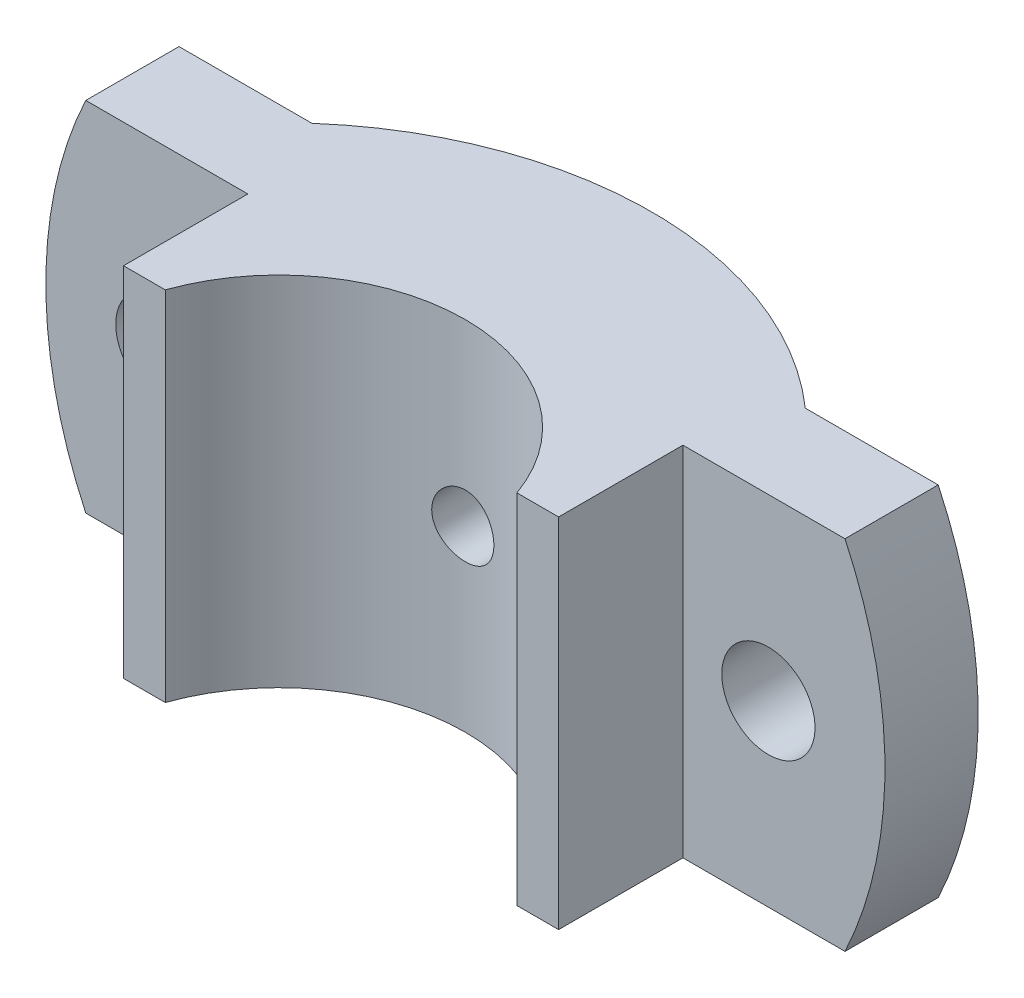
SolidWorks part; units mm, degrees
ref_plane "Front Plane" through (0, 0, 0) normal (0, 0, 1) x (1, 0, 0)
ref_plane "Top Plane" through (0, 0, 0) normal (0, 1, 0) x (1, 0, 0)
ref_plane "Right Plane" through (0, 0, 0) normal (1, 0, 0) x (0, 0, -1)
sketch "Sketch1" plane through (0, 0, 0) normal (0, 1, 0) x (1, 0, 0)
  line L0 (-67.1596, 0) -> (80.945, 0) construction
  line L1 (0, 82.0377) -> (0, -82.0377) construction
  line L2 (-54, 0) -> (-28, 0)
  line L3 (-54, 12) -> (-31.749, 12)
  line L4 (-28, -16) -> (-22.6274, -16)
  line L5 (22.6274, -16) -> (28, -16)
  line L6 (31.749, 12) -> (54, 12)
  line L7 (-54, 12) -> (-54, 0)
  line L8 (54, 12) -> (54, 0)
  line L9 (-28, 0) -> (-28, -16)
  line L10 (28, 0) -> (28, -16)
  line L11 (28, 0) -> (54, 0)
  arc A1 (22.6274, -16) -> (-22.6274, -16) centre (0, -24) ccw
  arc A2 (31.749, 12) -> (-31.749, 12) centre (0, -24) ccw
  point P7 (0, 24)
  dimension "D5" = 48
  dimension "D6" = 24
  dimension "D1" = 108
  dimension "D2" = 12
  dimension "D3" = 16
  dimension "D4" = 28
  dimension "D7" = 8
  dimension "D8" = 54
extrude "Boss-Extrude1" add sketch "Sketch1" along normal blind 46
sketch "Sketch2" plane through (0, 0, -12) normal (0, 0, -1) x (-1, 0, 0)
  line L0 (0, 57.651) -> (0, -11.651) construction
  line L1 (-77.2878, 23) -> (77.2878, 23) construction
  line L2 (-54, 46) -> (-48.8569, 46)
  line L3 (-54, 0) -> (-48.8569, 0)
  line L4 (-54, 46) -> (-54, 0)
  line L5 (54, 46) -> (54, 0)
  line L6 (39, 0) -> (39, 6)
  line L7 (48.8569, 46) -> (54, 46)
  line L8 (48.8569, 0) -> (54, 0)
  line L9 (-39, 46) -> (-39, 40)
  line L10 (-54, 46) -> (-31.749, 46) construction
  line L11 (-39, 0) -> (-39, 6)
  line L12 (39, 46) -> (39, 40)
  line L13 (-48.8569, 46) -> (-39, 46)
  line L14 (-48.8569, 0) -> (-39, 0)
  line L15 (48.8569, 46) -> (39, 46)
  line L16 (48.8569, 0) -> (39, 0)
  circle A0 centre (-39, 23) radius 6
  circle A1 centre (39, 23) radius 6
  arc A2 (-48.8569, 46) -> (-48.8569, 0) centre (0, 23) ccw
  arc A3 (48.8569, 0) -> (48.8569, 46) centre (0, 23) ccw
  arc A5 (-39, 6) -> (-39, 40) centre (-39, 23) ccw
  arc A6 (39, 6) -> (39, 40) centre (39, 23) cw
  point P11 (0, 23)
  line M4 (31.749, 0) -> (54, 0)
  line M5 (54, 0) -> (54, 46)
  line M6 (54, 46) -> (31.749, 46)
  line M7 (31.749, 46) -> (31.749, 0)
  dimension "D3" = 12
  dimension "D4" = 108
  dimension "D5" = 17
  dimension "D1" = 39
  dimension "D2" = 23
extrude "Cut-Extrude1" cut sketch "Sketch2" against normal through all contours A2 L2 L4 | A2 L4 L3 | A0 | A1 | A3 L5 M6 | A3 M4 M5 region at (52.4705, 40.3062, -12) region at (52.4705, 5.6938, -12) region at (-52.4705, 40.3062, -12) region at (-52.4705, 5.6938, -12) region at (39, 23, -12) region at (-39, 23, -12)
sketch "Sketch3" plane through (0, 0, -12) normal (0, 0, -1) x (-1, 0, 0)
  circle A0 centre (0, 23) radius 4
  arc A1 (-48.8569, 46) -> (-48.8569, 0) centre (0, 23) ccw construction
  point P6 (-54, 23)
  dimension "D1" = 8
extrude "Cut-Extrude2" cut sketch "Sketch3" against normal mid plane 48
extrude "Cut-Extrude4" cut sketch "Sketch2<5>" along normal blind 48 contours L11 A5 L9 L13 A2 L14 A0 | A6 L6 A3 L12 A1 M4 M6 M7 | A6 M7 region at (43.9285, 45.4396, -12) region at (-52.1999, 11.3275, -12) region at (-27.7342, 23, -12)
sketch "Sketch2<5>" plane through (0, 0, -12) normal (0, 0, -1) x (-1, 0, 0) same geometry as "Sketch2"
